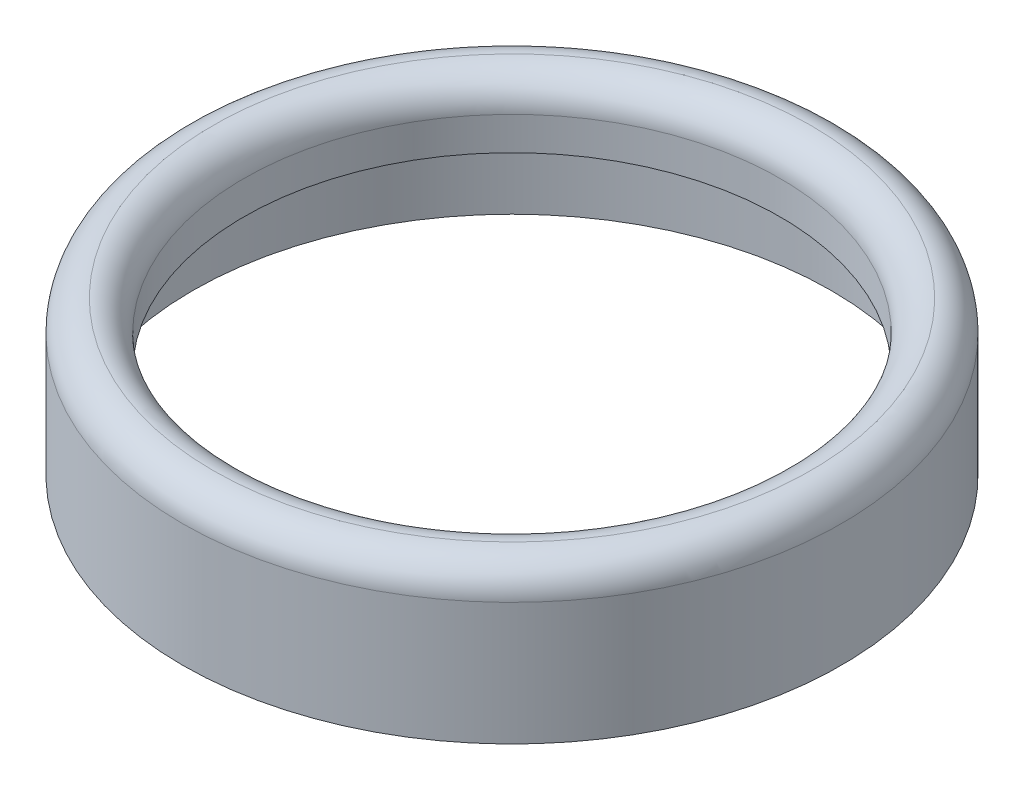
SolidWorks part; units mm, degrees
ref_plane "Front Plane" through (0, 0, 0) normal (0, 0, 1) x (1, 0, 0)
ref_plane "Top Plane" through (0, 0, 0) normal (0, 1, 0) x (1, 0, 0)
ref_plane "Right Plane" through (0, 0, 0) normal (1, 0, 0) x (0, 0, -1)
sketch "Sketch1" plane through (0, 0, 0) normal (0, 1, 0) x (1, 0, 0)
  circle A0 centre (0, 0) radius 25.8
  circle A1 centre (0, 0) radius 25
  dimension "D1" = 51.6
  dimension "D2" = 50
extrude "Boss-Extrude1" add sketch "Sketch1" against normal blind 7
sketch "Sketch2" plane through (0, 0, 0) normal (0, 1, 0) x (1, 0, 0)
  circle A0 centre (0, 0) radius 25.8
  circle A1 centre (0, 0) radius 21
  dimension "D1" = 42
  dimension "D2" = 51.6
extrude "Boss-Extrude2" add sketch "Sketch2" along normal blind 5
fillet "Fillet3" radius 2.4 2 edges at (0, 5, 21) (0, 5, 25.8)
